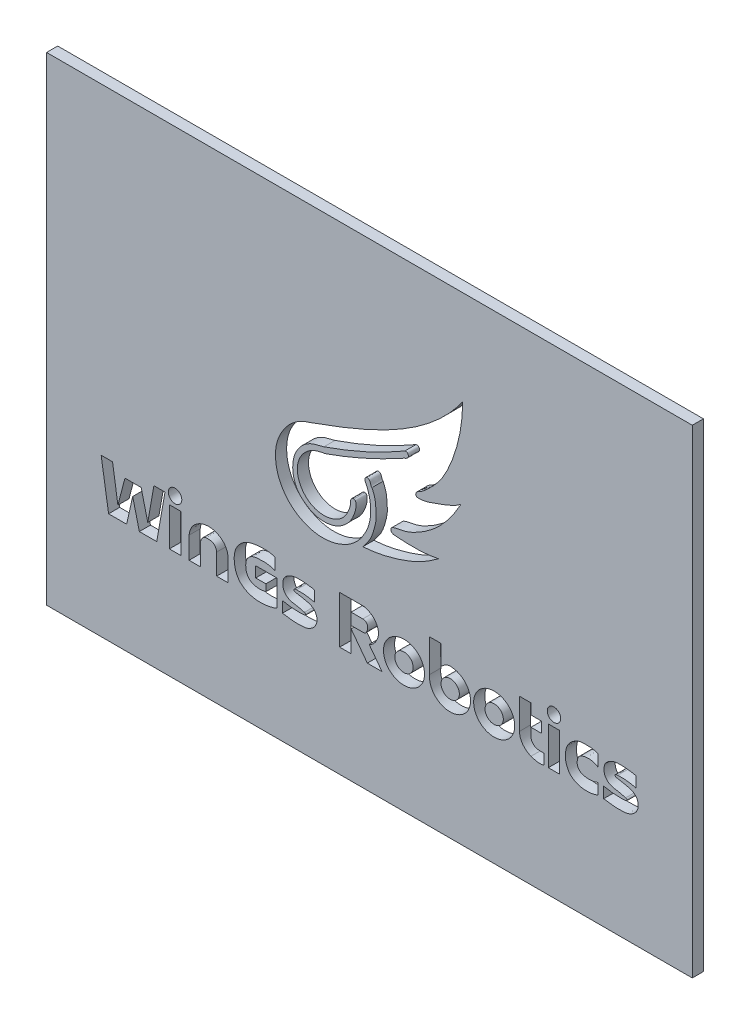
SolidWorks part; units mm, degrees
ref_plane "前视基准面" through (0, 0, 0) normal (0, 0, 1) x (1, 0, 0)
ref_plane "上视基准面" through (0, 0, 0) normal (0, 1, 0) x (1, 0, 0)
ref_plane "右视基准面" through (0, 0, 0) normal (1, 0, 0) x (0, 0, -1)
other "Configuration Table"
sketch "Sketch1" plane through (0, 0, 0) normal (0, 0, 1) x (1, 0, 0)
  line L1 (0, 0) -> (116, 0)
  line L2 (0, 0) -> (0, 86)
  line L3 (0, 86) -> (116, 86)
  line L4 (116, 0) -> (116, 86)
  dimension "D1" = 116
  dimension "D2" = 86
extrude "Boss-Extrude1" add sketch "Sketch1" along normal blind 2
sketch "Sketch2" plane through (0, 0, 2) normal (0, 0, 1) x (1, 0, 0)
  line L0 (9.8027, 28.235) -> (11.8527, 28.235)
  line L1 (11.8527, 28.235) -> (12.8123, 21.9684)
  line L2 (12.8123, 21.9684) -> (14.0773, 26.8101)
  line L3 (14.0773, 26.8101) -> (16.9852, 26.8101)
  line L4 (16.9852, 26.8101) -> (18.1775, 21.9684)
  line L5 (18.1775, 21.9684) -> (19.2825, 28.235)
  line L6 (19.2825, 28.235) -> (21.2744, 28.235)
  line L7 (21.2744, 28.235) -> (19.7853, 19.7903)
  line L8 (19.7853, 19.7903) -> (16.6653, 19.7903)
  line L9 (16.6653, 19.7903) -> (15.4678, 24.6536)
  line L10 (15.4678, 24.6536) -> (14.3826, 19.7903)
  line L11 (14.3826, 19.7903) -> (11.1403, 19.7903)
  line L12 (11.1403, 19.7903) -> (9.8027, 28.235)
  line L13 (22.0595, 26.6647) -> (24.1096, 26.6647)
  line L14 (24.1096, 26.6647) -> (24.1096, 19.7903)
  line L15 (24.1096, 19.7903) -> (22.0595, 19.7903)
  line L16 (22.0595, 19.7903) -> (22.0595, 26.6647)
  line L17 (32.5933, 23.6986) -> (32.5933, 19.7903)
  line L18 (32.5933, 19.7903) -> (30.5505, 19.7903)
  line L19 (30.5505, 19.7903) -> (30.5505, 23.5343)
  line L20 (27.6427, 23.5343) -> (27.6427, 19.7903)
  line L21 (27.6427, 19.7903) -> (25.5972, 19.7903)
  line L22 (25.5972, 19.7903) -> (25.5972, 23.6986)
  line L23 (41.4245, 20.2317) -> (41.4245, 24.9256)
  line L24 (41.4245, 24.9256) -> (37.5759, 24.9256)
  line L25 (37.5759, 24.9256) -> (37.5759, 23.026)
  line L26 (37.5759, 23.026) -> (39.3929, 23.026)
  line L27 (39.3929, 23.026) -> (39.3929, 21.7872)
  line L28 (41.0585, 28.009) -> (41.0585, 25.9029)
  line L29 (42.3726, 19.9426) -> (42.3726, 21.9041)
  line L30 (48.1482, 26.4281) -> (48.1482, 24.5174)
  line L31 (57.9509, 22.8769) -> (60.2681, 19.7995)
  line L32 (60.2681, 19.7995) -> (57.6234, 19.7995)
  line L33 (57.6234, 19.7995) -> (54.6991, 23.6831)
  line L34 (54.6991, 23.6831) -> (54.6991, 19.7995)
  line L35 (54.6991, 19.7995) -> (52.65, 19.7995)
  line L36 (52.65, 19.7995) -> (52.65, 28.3165)
  line L37 (52.65, 28.3165) -> (56.9933, 28.3165)
  line L38 (56.8114, 26.2746) -> (54.6991, 26.2746)
  line L39 (54.6991, 26.2746) -> (54.6991, 24.2045)
  line L40 (54.6991, 24.2045) -> (56.8948, 24.2045)
  line L41 (68.7934, 29.486) -> (70.8757, 29.486)
  line L42 (70.8757, 29.486) -> (70.8757, 25.9572)
  line L43 (68.7934, 29.486) -> (68.8194, 23.6311)
  line L44 (84.9748, 28.3165) -> (87.0193, 28.3165)
  line L45 (87.0193, 28.3165) -> (87.0193, 26.4281)
  line L46 (87.0193, 26.4281) -> (88.9274, 26.4281)
  line L47 (88.9274, 26.4281) -> (88.9274, 24.5174)
  line L48 (88.9274, 24.5174) -> (87.0193, 24.5174)
  line L49 (87.0193, 24.5174) -> (87.0193, 22.8769)
  line L50 (84.9748, 28.3165) -> (84.9748, 22.8769)
  line L51 (89.3697, 19.7903) -> (89.3697, 21.6564)
  line L52 (90.1423, 26.5997) -> (92.1233, 26.5997)
  line L53 (92.1233, 26.5997) -> (92.1233, 19.7903)
  line L54 (92.1233, 19.7903) -> (90.1423, 19.7903)
  line L55 (90.1423, 19.7903) -> (90.1423, 26.5997)
  line L56 (100.0817, 19.9352) -> (100.0817, 21.8967)
  line L57 (105.8573, 26.4207) -> (105.8573, 24.51)
  circle A0 centre (23.0773, 28.5403) radius 1.2139
  circle A1 centre (91.149, 28.5403) radius 1.2042
  ellipse E0 centre (64.2087, 23.2238) end of major axis (62.5755, 23.026) minor radius 1.6135
  ellipse E1 centre (64.2087, 23.2238) end of major axis (60.5207, 23.2238) minor radius 3.5863
  ellipse E2 centre (72.5089, 23.2351) end of major axis (70.8757, 23.0374) minor radius 1.6135
  ellipse E3 centre (72.4814, 23.2061) end of major axis (68.7937, 23.2519) minor radius 3.5627 (68.8194, 23.6311) -> (72.4501, 26.7688) ccw
  ellipse E4 centre (80.4111, 23.2582) end of major axis (78.7779, 23.0604) minor radius 1.6135
  ellipse E5 centre (80.4111, 23.2582) end of major axis (76.723, 23.2582) minor radius 3.5863
  spline S0 degree 3 poles (47.1831, 52.0268) (57.216, 55.6604) (68.3491, 59.9142) (74.7524, 69.0372) knots 0 0 0 0 1 1 1 1
  spline S1 degree 3 poles (74.7524, 69.0372) (74.7365, 65.3659) (73.7278, 60.4257) (70.9663, 54.8142) (68.7581, 52.5438) (67.3008, 51.2594) (66.3857, 50.8892) (66.1919, 50.0322) (67.3405, 50.0519) (68.5807, 50.2825) (71.1429, 51.2424) (73.2135, 51.9772) (74.4343, 52.9034) knots 0 0 0 0 0.360634 0.500005 0.614902 0.674582 0.691796 0.711227 0.738156 0.775636 0.851126 1 1 1 1
  spline S2 degree 3 poles (74.4343, 52.9034) (73.5344, 51.2446) (71.9363, 48.8706) (69.1717, 46.2263) (66.8129, 44.6852) (64.459, 43.5637) (62.7709, 43.442) (61.8385, 43.0103) (61.7928, 42.333) (62.306, 42.118) (62.5755, 42.1345) knots 0 0 0 0 0.317486 0.47747 0.639062 0.792073 0.904921 0.928219 0.95201 1 1 1 1
  spline S3 degree 3 poles (62.5755, 42.1345) (63.3547, 42.0538) (64.7001, 41.9914) (66.7084, 41.981) (68.5463, 42.1026) (69.8092, 42.2942) (70.4107, 42.4227) knots 0 0 0 0 0.298501 0.513418 0.765548 1 1 1 1
  spline S4 degree 3 poles (70.4107, 42.4227) (69.0722, 41.3928) (66.6735, 39.9566) (63.1137, 38.6779) (60.0189, 37.8594) (57.9209, 37.5758) (56.8114, 37.504) knots 0 0 0 0 0.345509 0.567874 0.772357 1 1 1 1
  spline S5 degree 3 poles (56.8114, 37.504) (57.1501, 38.014) (57.9873, 38.9045) (58.6132, 40.423) (59.0127, 41.8409) (59.2903, 43.2209) (59.1608, 44.4082) (59.1125, 45.8858) (58.7734, 46.8278) (58.4542, 47.5164) knots 0 0 0 0 0.171911 0.337536 0.453261 0.586014 0.727877 0.785411 1 1 1 1
  spline S6 degree 3 poles (58.4542, 47.5164) (58.1552, 47.7663) (58.2426, 48.4056) (57.6344, 48.7258) (57.3395, 48.5611) (57.1481, 48.3317) (57.1918, 47.9689) (57.3731, 47.5948) (57.6463, 47.0478) (57.8358, 46.4382) (58.0549, 45.6679) (58.1832, 44.9046) (58.2458, 43.8518) (58.2148, 42.7406) (57.9317, 41.5832) (57.6308, 40.6253) (57.1596, 39.7594) (56.5162, 38.6016) (55.4247, 37.4363) (54.1168, 36.4637) (52.8944, 35.9233) (51.7724, 35.5143) (50.4508, 35.3174) (48.7837, 35.2372) (46.8987, 35.6969) (44.9241, 36.6174) (43.1617, 38.1067) (42.0038, 39.9015) (41.341, 41.702) (41.0315, 43.7959) (41.2416, 46.0312) (42.3532, 48.424) (44.0891, 50.6501) (46.0639, 51.7314) (47.1831, 52.0268) knots 0 0 0 0 0.025484 0.033383 0.040232 0.046589 0.052344 0.063459 0.074884 0.093534 0.10647 0.129018 0.145625 0.17776 0.203591 0.22594 0.245355 0.270053 0.315285 0.351906 0.379455 0.405318 0.432327 0.469429 0.51742 0.561659 0.615846 0.670887 0.704018 0.744828 0.813277 0.85164 0.92215 1 1 1 1
  spline S7 degree 3 poles (64.3499, 56.1614) (64.4693, 56.198) (64.7382, 56.2478) (64.9298, 55.9871) (65.0268, 55.728) (64.8911, 55.1487) (64.274, 55.0547) (64.0386, 54.8823) knots 0 0 0 0 0.180535 0.288784 0.393192 0.542414 1 1 1 1
  spline S8 degree 3 poles (64.0386, 54.8823) (59.572, 52.4062) (54.9001, 50.2948) (50.0745, 48.6121) knots 0 0 0 0 1 1 1 1
  spline S9 degree 2 poles (64.3499, 56.1614) (57.4385, 52.1577) (49.8143, 49.5487) knots 0 0 0 1 1 1
  spline S10 degree 3 poles (49.8143, 49.5487) (49.1643, 49.3784) (48.2124, 49.1961) (46.3723, 48.3773) (44.2192, 46.161) (43.9774, 42.6043) (45.2254, 40.0525) (46.5951, 38.9146) (48.299, 37.9908) (50.179, 37.8379) (52.0127, 38.232) (53.3955, 39.1002) (54.5017, 40.1892) (55.1879, 41.4828) (55.5621, 42.6798) (55.6315, 43.5768) (55.4539, 44.1289) (55.208, 44.1161) knots 0 0 0 0 0.074167 0.1054 0.220595 0.394008 0.454413 0.527731 0.585289 0.665338 0.728528 0.788515 0.842168 0.897128 0.948286 0.97672 1 1 1 1
  spline S11 degree 3 poles (55.208, 44.1161) (55.0226, 44.1791) (54.667, 43.959) (54.6094, 43.4642) (54.5978, 42.8636) (54.3423, 42.0093) (53.7764, 40.7342) (52.3297, 39.3376) (50.1524, 38.7214) (47.7052, 39.1332) (45.9303, 40.6216) (44.9775, 42.794) (45.0428, 45.5373) (47.1244, 48.0082) (49.206, 48.4687) (50.0745, 48.6121) knots 0 0 0 0 0.023493 0.044042 0.061062 0.101136 0.156797 0.23921 0.350066 0.433771 0.549578 0.629423 0.732521 0.886291 1 1 1 1
  spline S12 degree 3 poles (25.5972, 23.6986) (25.655, 24.3658) (26.0941, 25.5117) (27.5424, 26.5737) (30.2768, 27.2067) (32.5736, 25.5619) (32.5933, 23.6986) knots 0 0 0 0 0.198571 0.34064 0.5135 1 1 1 1
  spline S13 degree 3 poles (30.5505, 23.5343) (30.5434, 23.9759) (30.1068, 24.7165) (29.076, 24.8585) (28.0074, 24.7723) (27.6729, 23.9331) (27.6427, 23.5343) knots 0 0 0 0 0.311205 0.495488 0.702071 1 1 1 1
  spline S14 degree 3 poles (41.0585, 28.009) (40.0534, 28.3395) (38.2528, 28.3483) (35.58, 27.8618) (33.8071, 26.0118) (33.5909, 23.4895) (34.2599, 21.0828) (36.5954, 19.6795) (39.0686, 19.544) (40.7235, 19.9364) (41.4245, 20.2317) knots 0 0 0 0 0.156695 0.267521 0.399378 0.502862 0.637623 0.747872 0.886035 1 1 1 1
  spline S15 degree 3 poles (39.3929, 21.7872) (38.7093, 21.6487) (37.5769, 21.5423) (36.1025, 22.3452) (35.7049, 23.7435) (35.8131, 25.2008) (36.9698, 26.204) (38.2345, 26.2733) (39.6234, 26.3182) (40.5236, 26.0878) (41.0585, 25.9029) knots 0 0 0 0 0.181467 0.284135 0.402884 0.534993 0.639881 0.765013 0.852735 1 1 1 1
  spline S16 degree 2 poles (48.1482, 24.5174) (46.544, 24.9457) (44.8888, 24.8527) knots 0 0 0 1 1 1
  spline S17 degree 2 poles (44.8888, 24.8527) (44.6892, 24.8488) (44.5108, 24.7528) knots 0 0 0 1 1 1
  spline S18 degree 3 poles (44.5108, 24.7528) (44.4063, 24.7177) (44.3879, 24.4124) (44.7022, 24.3838) (44.8061, 24.3456) knots 0 0 0 0 0.400794 1 1 1 1
  spline S19 degree 3 poles (44.8061, 24.3456) (45.4236, 24.274) (46.288, 24.0648) (47.4629, 23.8067) (48.147, 23.319) (48.5456, 22.5902) (48.6196, 21.7633) (48.3197, 20.8064) (47.5722, 20.1396) (46.6088, 19.7108) (45.569, 19.6812) (44.1213, 19.6404) (43.0613, 19.8702) (42.3726, 19.9426) knots 0 0 0 0 0.150366 0.217158 0.290606 0.346071 0.414261 0.48693 0.581715 0.647373 0.740089 0.830727 1 1 1 1
  spline S20 degree 3 poles (42.3726, 21.9041) (42.8525, 21.8037) (43.5405, 21.6847) (44.4782, 21.597) (45.1945, 21.5883) (45.8688, 21.5828) (46.3005, 21.6313) (46.5297, 21.6877) (46.5567, 21.797) (46.5523, 21.9643) (46.379, 22.021) (46.3173, 22.049) knots 0 0 0 0 0.315552 0.449833 0.605449 0.778844 0.876435 0.89782 0.91722 0.942476 1 1 1 1
  spline S21 degree 3 poles (46.3173, 22.049) (45.8247, 22.2107) (44.9758, 22.4016) (43.6481, 22.557) (42.7017, 23.2519) (42.4205, 24.1635) (42.4311, 24.8543) (42.5725, 25.4907) (43.0041, 26.0044) (43.5079, 26.3588) (44.1094, 26.601) (44.7443, 26.7343) (45.4456, 26.7433) (46.2623, 26.7426) (47.164, 26.593) (47.8325, 26.5196) (48.1482, 26.4281) knots 0 0 0 0 0.129354 0.21684 0.332807 0.395282 0.447956 0.504879 0.55359 0.611568 0.6573 0.714661 0.772387 0.8321 0.918346 1 1 1 1
  spline S22 degree 3 poles (56.9933, 28.3165) (57.5079, 28.1999) (58.406, 27.8613) (59.3049, 26.8025) (59.7648, 25.5393) (59.3451, 23.9707) (58.5781, 23.1135) (57.9509, 22.8769) knots 0 0 0 0 0.216647 0.372499 0.551297 0.738033 1 1 1 1
  spline S23 degree 3 poles (56.8114, 26.2746) (57.1651, 26.312) (57.7627, 25.8573) (57.663, 24.8197) (57.3325, 24.1932) (56.8948, 24.2045) knots 0 0 0 0 0.345185 0.626261 1 1 1 1
  spline S24 degree 3 poles (70.8757, 25.9572) (71.1665, 26.2093) (71.6761, 26.5782) (72.2834, 26.7779) (72.5256, 26.7686) knots 0 0 0 0 0.616176 1 1 1 1
  spline S25 degree 3 poles (84.9748, 22.8769) (84.9049, 21.5816) (85.8804, 20.4707) (87.0193, 20.0095) knots 0 0 0 0 1 1 1 1
  spline S26 degree 3 poles (87.0193, 20.0095) (87.7648, 19.7661) (88.5925, 19.5177) (89.3697, 19.7903) knots 0 0 0 0 1 1 1 1
  spline S27 degree 3 poles (89.3697, 21.6564) (88.8864, 21.6815) (88.1032, 21.5524) (87.2817, 22.1652) (87.0872, 22.6179) (87.0193, 22.8769) knots 0 0 0 0 0.51466 0.724878 1 1 1 1
  spline S28 degree 1 poles (99.1074, 26.4281) (99.0451, 24.3456) knots 0 0 1 1
  spline S29 degree 1 poles (99.0451, 21.9684) (99.0762, 20.0095) knots 0 0 1 1
  spline S30 degree 3 poles (99.0451, 24.3456) (98.1408, 24.9177) (96.9334, 25.0104) (95.9622, 24.5174) knots 0 0 0 0 1 1 1 1
  spline S31 degree 3 poles (95.9622, 24.5174) (95.5905, 24.3596) (95.3714, 23.8067) (95.285, 23.0241) (95.4658, 22.3958) (95.9075, 21.9602) (96.4713, 21.7289) (97.5261, 21.5847) (98.4341, 21.6572) (99.0451, 21.9684) knots 0 0 0 0 0.178932 0.272004 0.383259 0.483726 0.563109 0.676721 1 1 1 1
  spline S32 degree 3 poles (99.1074, 26.4281) (98.7068, 26.5706) (98.0571, 26.739) (97.1441, 26.7697) (96.4259, 26.789) (95.6235, 26.6801) (94.7667, 26.291) (94.0187, 25.6423) (93.3941, 24.7521) (93.1988, 23.7089) (93.1885, 22.6621) (93.4504, 21.6401) (94.6922, 19.4323) (97.6705, 19.3697) (99.0762, 20.0095) knots 0 0 0 0 0.080032 0.124598 0.171299 0.214887 0.2755 0.344981 0.398822 0.476451 0.539473 0.594477 0.673245 1 1 1 1
  spline S33 degree 2 poles (105.8573, 24.51) (104.2531, 24.9383) (102.5979, 24.8453) knots 0 0 0 1 1 1
  spline S34 degree 2 poles (102.5979, 24.8453) (102.3983, 24.8414) (102.2199, 24.7454) knots 0 0 0 1 1 1
  spline S35 degree 3 poles (102.2199, 24.7454) (102.1154, 24.7103) (102.097, 24.405) (102.4113, 24.3764) (102.5152, 24.3382) knots 0 0 0 0 0.400794 1 1 1 1
  spline S36 degree 3 poles (102.5152, 24.3382) (103.1327, 24.2666) (103.9971, 24.0574) (105.172, 23.7993) (105.8561, 23.3116) (106.2547, 22.5828) (106.3287, 21.7559) (106.0288, 20.799) (105.2813, 20.1322) (104.3179, 19.7034) (103.2781, 19.6738) (101.8304, 19.633) (100.7704, 19.8627) (100.0817, 19.9352) knots 0 0 0 0 0.150366 0.217158 0.290606 0.346071 0.414261 0.48693 0.581715 0.647373 0.740089 0.830727 1 1 1 1
  spline S37 degree 3 poles (100.0817, 21.8967) (100.5616, 21.7963) (101.2496, 21.6773) (102.1873, 21.5896) (102.9036, 21.5809) (103.5779, 21.5754) (104.0096, 21.6239) (104.2387, 21.6803) (104.2658, 21.7896) (104.2614, 21.9568) (104.0881, 22.0136) (104.0264, 22.0416) knots 0 0 0 0 0.315552 0.449833 0.605449 0.778844 0.876435 0.89782 0.91722 0.942476 1 1 1 1
  spline S38 degree 3 poles (104.0264, 22.0416) (103.5338, 22.2033) (102.6849, 22.3942) (101.3572, 22.5496) (100.4108, 23.2445) (100.1296, 24.1561) (100.1402, 24.8468) (100.2816, 25.4833) (100.7132, 25.997) (101.217, 26.3514) (101.8185, 26.5936) (102.4534, 26.7269) (103.1547, 26.7359) (103.9714, 26.7352) (104.8731, 26.5856) (105.5416, 26.5122) (105.8573, 26.4207) knots 0 0 0 0 0.129354 0.21684 0.332807 0.395282 0.447956 0.504879 0.55359 0.611568 0.6573 0.714661 0.772387 0.8321 0.918346 1 1 1 1
extrude "Cut-Extrude1" cut sketch "Sketch2" against normal blind 11 contours S6 S5 S4 S3 S2 S1 S0 S11 S10 S9 S7 S8 | L12 L11 L10 L9 L8 L7 L6 L5 L4 L3 L2 L1 L0 | L16 L15 L14 L13 | A0 | S13 L19 L18 L17 S12 L22 L21 L20 | L27 S15 L28 S14 L23 L24 L25 L26 | S21 S20 L29 S19 S18 S17 S16 L30 | S22 L37 L36 L35 L34 L33 L32 L31 L38 S23 L40 L39 | E1 E0 | S24 L42 L41 L43 E3 E2 | E5 E4 | L51 S27 L49 L48 L47 L46 L45 L44 L50 S25 S26 | L55 L54 L53 L52 | A1 | S28 S32 S29 S31 S30 | S38 S37 L56 S36 S35 S34 S33 L57 region at (10.8277, 28.0925, 2) region at (23.0846, 23.2275, 2) region at (32.4942, 21.7444, 2) region at (37.7958, 23.8436, 2) region at (45.411, 23.1442, 2) region at (55.8853, 24.1982, 2) region at (69.8346, 29.363, 2) region at (86.7675, 23.9164, 2) region at (91.1328, 23.195, 2) region at (103.1201, 23.1368, 2) region at (23.0773, 28.5403, 2) region at (91.149, 28.5403, 2) region at (67.7938, 23.2238, 2) region at (83.9962, 23.2582, 2) region at (58.19, 48.478, 2) region at (98.9834, 25.3896, 2)
